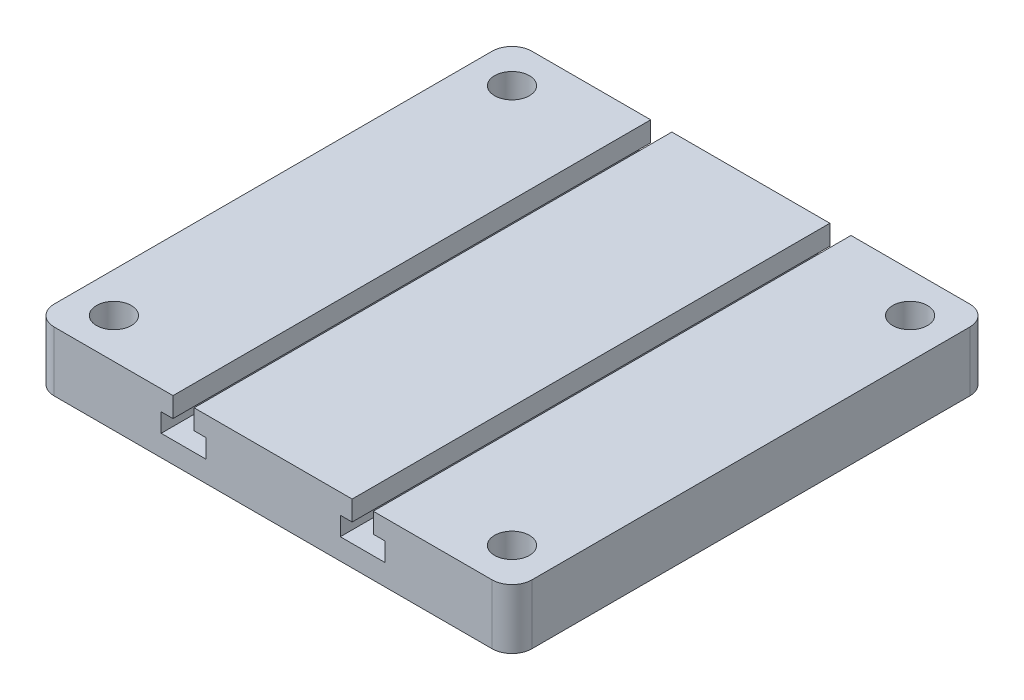
SolidWorks part; units mm, degrees
material "Delrin 2700 NC010, Low Viscosity Acetal Copolymer (SS)"
ref_plane "Front" through (0, 0, 0) normal (0, 0, 1) x (1, 0, 0)
ref_plane "Top" through (0, 0, 0) normal (0, 1, 0) x (1, 0, 0)
ref_plane "Right" through (0, 0, 0) normal (1, 0, 0) x (0, 0, -1)
sketch "Sketch1" plane through (0, 0, 0) normal (0, 1, 0) x (1, 0, 0)
  line L1 (-76.2, 76.2) -> (76.2, 76.2)
  line L2 (-76.2, 76.2) -> (-76.2, -76.2)
  line L3 (-76.2, -76.2) -> (76.2, -76.2)
  line L4 (76.2, 76.2) -> (76.2, -76.2)
  line L5 (-76.2, 76.2) -> (76.2, -76.2) construction
  line L6 (-76.2, -76.2) -> (76.2, 76.2) construction
  point P0 (0, 0)
  dimension "D1" = 152.4
  dimension "D2" = 152.4
extrude "Boss-Extrude1" add sketch "Sketch1" along normal blind 19.05
hole_wizard "CBORE for 1/4 Socket Head Cap Screw1" positions "Sketch2" profile "Sketch3" counterbore size "1/4" standard "ANSI Inch" end condition through all
sketch "Sketch2" plane through (0, 19.05, 0) normal (0, 1, 0) x (1, 0, 0)
  line L1 (-63.5, 63.5) -> (63.5, 63.5) construction
  line L2 (-63.5, 63.5) -> (-63.5, -63.5) construction
  line L3 (-63.5, -63.5) -> (63.5, -63.5) construction
  line L4 (63.5, 63.5) -> (63.5, -63.5) construction
  line L5 (-63.5, 63.5) -> (63.5, -63.5) construction
  line L6 (-63.5, -63.5) -> (63.5, 63.5) construction
  point P0 (-63.5, 63.5)
  point P2 (63.5, 63.5)
  point P4 (63.5, -63.5)
  point P6 (-63.5, -63.5)
  point P108 (0, 0)
  dimension "D1" = 127
  dimension "D2" = 127
sketch "Sketch3" plane through (-63.5, 19.05, -63.5) normal (1, 0, 0) x (0, 0, 1)
  line L0 (0, 0) -> (0, 19.05)
  line L1 (0, 19.05) -> (3.2639, 19.05)
  line L3 (3.2639, 19.05) -> (3.2639, 8.89)
  line L4 (3.2639, 8.89) -> (5.5562, 8.89)
  line L5 (5.5562, 8.89) -> (5.5562, 0)
  line L7 (5.5562, 0) -> (0, 0)
  line L11 (0, -6.35) -> (0, 107.95) construction
  dimension "Thru Hole Dia." = 6.5278
  dimension "Thru Hole Depth" = 19.05
  dimension "C'Bore Dia." = 11.1125
  dimension "C'Bore Depth" = 8.89
sketch "Sketch4" plane through (0, 0, 76.2) normal (0, 0, 1) x (1, 0, 0)
  line L0 (-31.9484, 19.05) -> (-31.9484, 12.7)
  line L1 (-76.2, 19.05) -> (76.2, 19.05) construction
  line L2 (-31.9484, 12.7) -> (-35.7188, 12.7)
  line L3 (-35.7188, 12.7) -> (-35.7188, 6.7469)
  line L4 (-35.7188, 6.7469) -> (-21.4312, 6.7469)
  line L5 (-21.4312, 6.7469) -> (-21.4312, 12.7)
  line L6 (-21.4312, 12.7) -> (-25.2016, 12.7)
  line L7 (-25.2016, 12.7) -> (-25.2016, 19.05)
  line L8 (0, 0) -> (0, 19.05) construction
  line L9 (-28.575, 6.7469) -> (-28.575, 19.05) construction
  line L10 (28.575, 6.7469) -> (28.575, 19.05) construction
  line L11 (25.2016, 12.7) -> (25.2016, 19.05)
  line L12 (21.4312, 12.7) -> (25.2016, 12.7)
  line L13 (21.4312, 6.7469) -> (21.4312, 12.7)
  line L14 (35.7188, 6.7469) -> (21.4312, 6.7469)
  line L15 (35.7188, 12.7) -> (35.7188, 6.7469)
  line L16 (31.9484, 12.7) -> (35.7188, 12.7)
  line L17 (31.9484, 19.05) -> (31.9484, 12.7)
  line L18 (-31.9484, 19.05) -> (-25.2016, 19.05)
  line L19 (25.2016, 19.05) -> (31.9484, 19.05)
  line L20 (-76.2, 0) -> (76.2, 0) construction
  dimension "D1" = 14.2875
  dimension "D2" = 6.7469
  dimension "D3" = 6.35
  dimension "D4" = 57.15
  dimension "D5" = 5.9531
  dimension "D6" = 6.7469
extrude "T-SLOT CUT WITH MCMASTER 8789A16 BIT" cut sketch "Sketch4" against normal through all
fillet "Fillet1" radius 6.35 4 edges at (-76.2, 9.525, 76.2) (76.2, 9.525, 76.2) (76.2, 9.525, -76.2) (-76.2, 9.525, -76.2)
